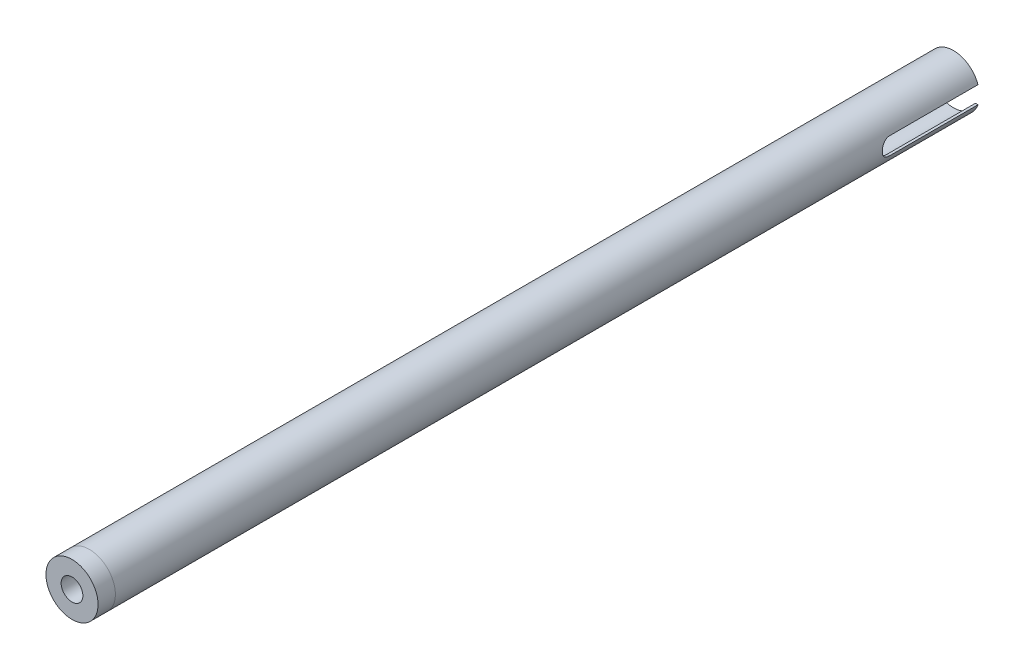
SolidWorks part; units mm, degrees
material "AISI 4130 Steel, annealed at 865C"
ref_plane "Front Plane" through (0, 0, 0) normal (0, 0, 1) x (1, 0, 0)
ref_plane "Top Plane" through (0, 0, 0) normal (0, 1, 0) x (1, 0, 0)
ref_plane "Right Plane" through (0, 0, 0) normal (1, 0, 0) x (0, 0, -1)
sketch "Axis" plane through (0, 0, 0) normal (0, 1, 0) x (1, 0, 0)
  line L0 (0, 0) -> (0, 322.3896) construction
  line L1 (0, 0) -> (0, -28.575) construction
  line L2 (0, 322.3896) -> (-9.525, 322.3896) construction
  line L4 (0, 356.4735) -> (-23.5893, 272.0626) construction
  dimension "D1" = 28.575
  dimension "D2" = 9.525
sketch "Sketch1" plane through (0, 0, 0) normal (0, 0, 1) x (1, 0, 0)
  line L0 (-9.525, 0) -> (9.525, 0) construction
  line L1 (-8.9803, 3.175) -> (8.9803, 3.175)
  line L2 (-8.9803, -3.175) -> (8.9803, -3.175)
  circle A0 centre (0, 0) radius 9.525
  circle A1 centre (0, 0) radius 8.636
  circle A2 centre (0, 0) radius 3.9688
  dimension "D1" = 19.05
  dimension "D3" = 7.9375
  dimension "D2" = 0.889
  dimension "D4" = 6.35
extrude "Threaded insert 1-1" add sketch "Sketch1" against normal blind 6.35 contours A2 L1 A1 | A1 L1 A0 | A2 L0 A1 L1 | A1 L0 A0 L1 | L0 A1 L2 A0 | L0 A2 L2 A1 | A2 L2 A1 | A1 L2 A0 | L0 A1 L2 A2 | L0 A0 L2 A1 | A0 L0 A1 L1 | A1 L0 A2 L1 region at (5.9465, 1.6355, 0) region at (5.9465, -1.6355, 0) region at (8.8881, 1.6046, 0) region at (8.8881, -1.6046, 0) region at (-5.9465, -1.6355, 0) region at (-5.9465, 1.6355, 0) region at (0, 5.5139, 0) region at (0, -5.5139, 0) region at (0, 8.8265, 0) region at (8.5057, -3.3655, 0) region at (-8.8881, -1.6046, 0) region at (-8.8881, 1.6046, 0)
extrude "Threaded insert 1-2" add sketch "Sketch1<3>" against normal blind 9.525 from surface contours A2 L1 A1 | A2 L0 A1 L1 | L0 A2 L2 A1 | A2 L2 A1 | L0 A1 L2 A2 | A1 L0 A2 L1 region at (5.9465, 1.6355, 0) region at (5.9465, -1.6355, 0) region at (-5.9465, -1.6355, 0) region at (-5.9465, 1.6355, 0) region at (0, 5.5139, 0) region at (0, -5.5139, 0) starting at face at (9.525, 0, -6.35)
sketch "Sketch1<3>" plane through (0, 0, 0) normal (0, 0, 1) x (1, 0, 0) same geometry as "Sketch1"
extrude "A-arm tube" add sketch "Sketch1<4>" against normal up to vertex (322.3896 mm away) from surface separate body contours A1 L1 A0 | A1 L0 A0 L1 | L0 A1 L2 A0 | A1 L2 A0 | L0 A0 L2 A1 | A0 L0 A1 L1 region at (8.8881, 1.6046, 0) region at (8.8881, -1.6046, 0) region at (0, 8.8265, 0) region at (8.5057, -3.3655, 0) region at (-8.8881, -1.6046, 0) region at (-8.8881, 1.6046, 0) up to point (0, 0, -322.3896) starting at face at (8.636, 0, -6.35)
sketch "Sketch1<4>" plane through (0, 0, 0) normal (0, 0, 1) x (1, 0, 0) same geometry as "Sketch1"
extrude "Apex slot" cut sketch "Sketch1<5>" along normal blind 35.56 from surface contours A0 L0 A1 L1 | L0 A0 L2 A1 | A1 L0 A0 L1 | L0 A1 L2 A0 region at (8.8881, 1.6046, 0) region at (8.8881, -1.6046, 0) region at (-8.8881, -1.6046, 0) region at (-8.8881, 1.6046, 0) starting at face at (8.636, 0, -322.3896)
sketch "Sketch1<5>" plane through (0, 0, 0) normal (0, 0, 1) x (1, 0, 0) same geometry as "Sketch1"
fillet "Fillet1" radius 3.175 4 edges at (-8.5057, 3.175, -286.8296) (-8.5057, -3.175, -286.8296) (8.5057, -3.175, -286.8296) (8.5057, 3.175, -286.8296)
equation "\"tube diameter\"= 3 / 4"
equation "\"tube thickness\"= .035"
equation "\"apex thickness\"= .25"
equation "\"tube slot\"= 1.4"
equation "\"D1@Sketch1\"=\"tube diameter\""
equation "\"D2@Sketch1\"=\"tube thickness\""
equation "\"threaded insert hole\"= .3125"
equation "\"D3@Sketch1\"=\"threaded insert hole\""
equation "\"D4@Sketch1\"=\"apex thickness\""
equation "\"D1@Apex slot\" = \"tube slot\""
equation "\"D1@Fillet1\"=\"apex thickness\"/2"
equation "\"D2@Axis\"=\"tube diameter\"/2"
